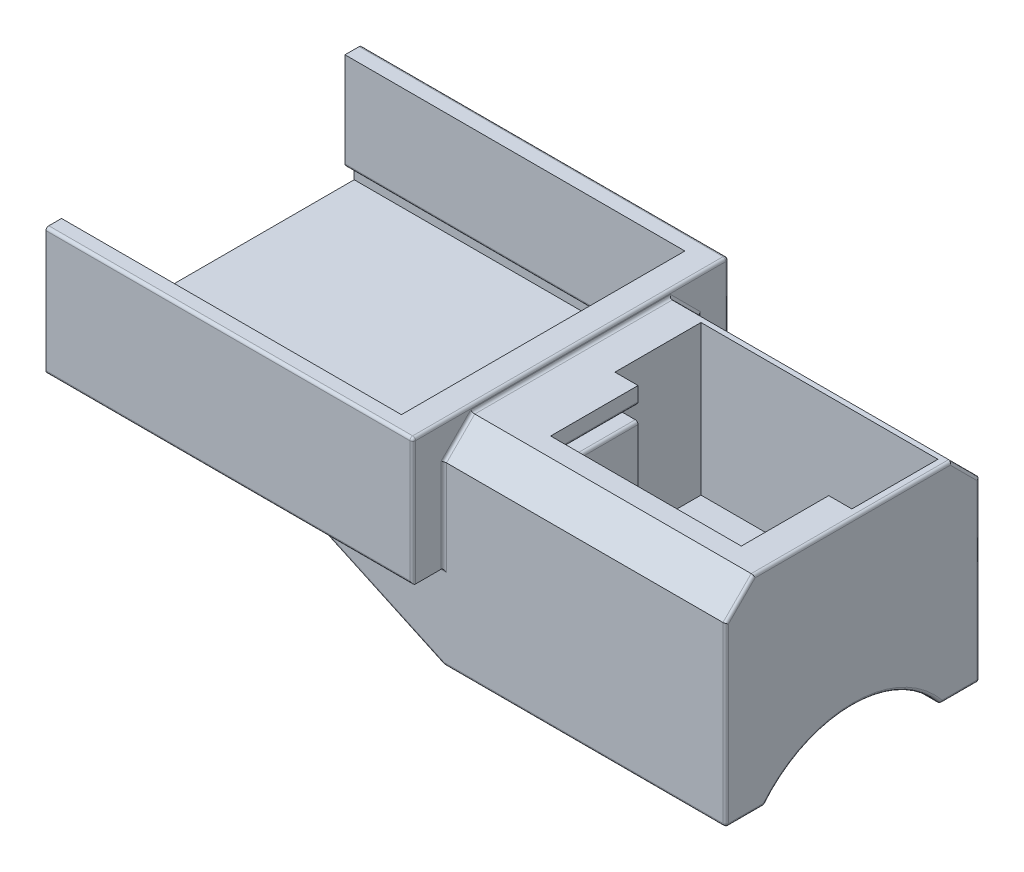
SolidWorks part; units mm, degrees
ref_plane "Front Plane" through (0, 0, 0) normal (0, 0, 1) x (1, 0, 0)
ref_plane "Top Plane" through (0, 0, 0) normal (0, 1, 0) x (1, 0, 0)
ref_plane "Right Plane" through (0, 0, 0) normal (1, 0, 0) x (0, 0, -1)
sketch "Sketch1" plane through (0, 0, 0) normal (0, 1, 0) x (1, 0, 0)
  line L1 (-65, -56) -> (65, -56)
  line L2 (-65, -56) -> (-65, 56)
  line L3 (-65, 56) -> (65, 56)
  line L4 (65, -56) -> (65, 56)
  line L5 (-65, -56) -> (65, 56) construction
  line L6 (-65, 56) -> (65, -56) construction
  point P0 (0, 0)
  dimension "D1" = 112
  dimension "D2" = 130
extrude "Boss-Extrude1" add sketch "Sketch1" along normal blind 45 contours L2 L1 L4 L3
sketch "Sketch3" plane through (-65, 0, 0) normal (-1, 0, 0) x (0, 0, 1)
  line L0 (56, 45) -> (-56, 45) construction
  line L1 (-50, 45) -> (50.5, 45)
  line L2 (-50, 45) -> (-50, 10.5)
  line L3 (-50, 10.5) -> (50.5, 10.5)
  line L4 (50.5, 45) -> (50.5, 10.5)
  line L5 (-56, 45) -> (-56, 0) construction
  line L6 (-53.25, 10.5) -> (53.75, 10.5)
  line L7 (-53.25, 10.5) -> (-53.25, 5)
  line L8 (-53.25, 5) -> (53.75, 5)
  line L9 (53.75, 10.5) -> (53.75, 5)
  line M11 (56, 45) -> (-56, 45)
  dimension "D1" = 34.5
  dimension "D2" = 5.5
  dimension "D3" = 100.5
  dimension "D4" = 3.25
  dimension "D5" = 107
  dimension "D6" = 6
extrude "Cut-Extrude1" cut sketch "Sketch3" against normal blind 120.5 contours L4 L2 L3 M11 | L9 L6 L3 L7 L8 region at (-65, 27.75, 0.25) region at (-65, 7.75, 0.25)
fillet "Fillet1" radius 1 2 edges at (-4.75, 10.5, 50.5) (-4.75, 10.5, -50)
sketch "Sketch5" plane through (65, 0, 0) normal (1, 0, 0) x (0, 0, -1)
  line L0 (0, 0) -> (0, -55) construction
  line L2 (-45, -30) -> (45, -30)
  line L3 (-45, -30) -> (-45, 35)
  line L4 (-45, 35) -> (45, 35)
  line L5 (45, -30) -> (45, 35)
  line L6 (0, 35) -> (0, 0) construction
  line L7 (-56, 45) -> (56, 45) construction
  circle A0 centre (0, -55) radius 40
  line M8 (-56, 0) -> (56, 0)
  dimension "D2" = 80
  dimension "D1" = 55
  dimension "D3" = 65
  dimension "D4" = 90
  dimension "D5" = 10
extrude "Boss-Extrude2" add sketch "Sketch5" along normal blind 100 contours L2 A0 | A0 L2 L5 L3 M8 | L5 L4 L3 M8 region at (65, -12.1667, 0) region at (65, -23.8917, 0) region at (65, 17.5, 0)
fillet "Fillet2" radius 1 7 edges at (0, 45, -56) (65, 22.5, -56) (0, 0, -56) (65, 45, 0) (0, 45, 56) (65, 22.5, 56) (0, 0, 56)
sketch "Sketch6" plane through (0, 35, 0) normal (0, 1, 0) x (1, 0, 0)
  line L0 (165, 0) -> (65, 0) construction
  line L1 (78, 2.7) -> (162, 2.7)
  line L2 (78, 2.7) -> (78, -28.3)
  line L3 (78, -28.3) -> (162, -28.3)
  line L4 (162, 2.7) -> (162, -28.3)
  line L6 (165, -45) -> (165, 45) construction
  line L7 (65, -45) -> (65, 45) construction
  line L8 (115, 0) -> (115, -12.8) construction
  line L9 (78, -12.8) -> (162, -12.8) construction
  point P14 (0, 0)
  dimension "D1" = 12.8
  dimension "D2" = 31
  dimension "D3" = 84
  dimension "D4" = 3
extrude "Cut-Extrude4" cut sketch "Sketch6" against normal blind 45.3
sketch "Sketch7" plane through (0, 0, -45) normal (0, 0, -1) x (-1, 0, 0)
  line L0 (-65, -30) -> (0, 0)
  line L1 (0, 0) -> (-65, 0)
  line L2 (-65, 0) -> (-65, -30)
extrude "Boss-Extrude3" add sketch "Sketch7" against normal blind 90
extrude "Cut-Extrude5" cut sketch "Sketch5<5>" along normal through all and the other way through all contours L2 A0 region at (65, -23.8917, 0)
sketch "Sketch5<5>" plane through (65, 0, 0) normal (1, 0, 0) x (0, 0, -1) same geometry as "Sketch5"
sketch "Sketch8" plane through (0, 35, 0) normal (0, 1, 0) x (1, 0, 0)
  line L1 (65, 45) -> (165, 45)
  line L2 (65, 45) -> (65, -45)
  line L3 (65, -45) -> (165, -45)
  line L4 (165, 45) -> (165, -45)
  line L5 (78, 2.7) -> (162, 2.7)
  line L6 (78, 2.7) -> (78, -28.3)
  line L7 (78, -28.3) -> (162, -28.3)
  line L8 (162, 2.7) -> (162, -28.3)
extrude "Boss-Extrude4" add sketch "Sketch8" along normal blind 1.7
sketch "Sketch9" plane through (0, 36.7, 0) normal (0, 1, 0) x (1, 0, 0)
  line L0 (162, 2.7) -> (78, 2.7) construction
  line L1 (86.2, 2.7) -> (153.8, 2.7)
  line L2 (86.2, 2.7) -> (86.2, -28.3)
  line L3 (86.2, -28.3) -> (153.8, -28.3)
  line L4 (153.8, 2.7) -> (153.8, -28.3)
  line L5 (78, -28.3) -> (162, -28.3) construction
  line L6 (78, 2.7) -> (78, -28.3) construction
  line L7 (162, -28.3) -> (162, 2.7) construction
  line L9 (65, 45) -> (165, 45)
  line L10 (65, 45) -> (65, -45)
  line L11 (65, -45) -> (165, -45)
  line L12 (165, 45) -> (165, -45)
  dimension "D1" = 8.2
  dimension "D2" = 8.2
extrude "Boss-Extrude5" add sketch "Sketch9" along normal blind 6
sketch "Sketch10" plane through (0, 42.7, 0) normal (0, 1, 0) x (1, 0, 0)
  line L0 (162, 2.7) -> (78, 2.7) construction
  line L1 (78, 2.7) -> (162, 2.7)
  line L2 (78, 2.7) -> (78, 33.2)
  line L3 (78, 33.2) -> (162, 33.2)
  line L4 (162, 2.7) -> (162, 33.2)
  line L5 (86.2, 2.7) -> (86.2, -28.3) construction
  line L6 (153.8, -28.3) -> (153.8, 2.7) construction
  dimension "D1" = 8.2
  dimension "D2" = 8.2
  dimension "D3" = 30.5
extrude "Cut-Extrude6" cut sketch "Sketch10" against normal blind 53
sketch "Sketch11" plane through (0, -10.3, 0) normal (0, 1, 0) x (1, 0, 0)
  line L0 (86.2, -28.3) -> (153.8, -28.3) construction
  line L1 (78, 2.7) -> (86.2, 2.7)
  line L2 (78, 2.7) -> (78, -28.3)
  line L3 (78, -28.3) -> (86.2, -28.3)
  line L4 (86.2, 2.7) -> (86.2, -28.3)
  line L5 (78, -28.3) -> (162, -28.3) construction
  line L7 (153.8, 2.7) -> (162, 2.7)
  line L8 (153.8, 2.7) -> (153.8, -28.3)
  line L9 (153.8, -28.3) -> (162, -28.3)
  line L10 (162, 2.7) -> (162, -28.3)
extrude "Boss-Extrude6" add sketch "Sketch11" along normal blind 42
chamfer "Chamfer1" distance 10 angle 45 2 edges at (115, 42.7, -45) (115, 42.7, 45)
fillet "Fillet3" radius 1 29 edges at (32.5, -15, -45) (115, -30, 31.225) (165, -15, 0) (115, -30, -31.225) (32.5, -15, 0) (65, -30, -38.1125) (115, -30, -45) (165, -30, -38.1125) (165, -30, 38.1125) (65, -30, 38.1125) (32.5, -15, 45) (115, -30, 45) (165, 1.35, -45) (165, 37.7, -40) (165, 42.7, 0) (165, 37.7, 40) (165, 1.35, 45) (32.5, 0, -45) (0, 0, 0) (32.5, 0, 45) (65, 16.35, -45) (65, 37.7, -40) (65, 16.35, 45) (65, 37.7, 40) (65, 42.7, 0) (153.8, 36.7, 12.8) (153.8, 31.7, 12.8) (86.2, 31.7, 12.8) (86.2, 36.7, 12.8)
